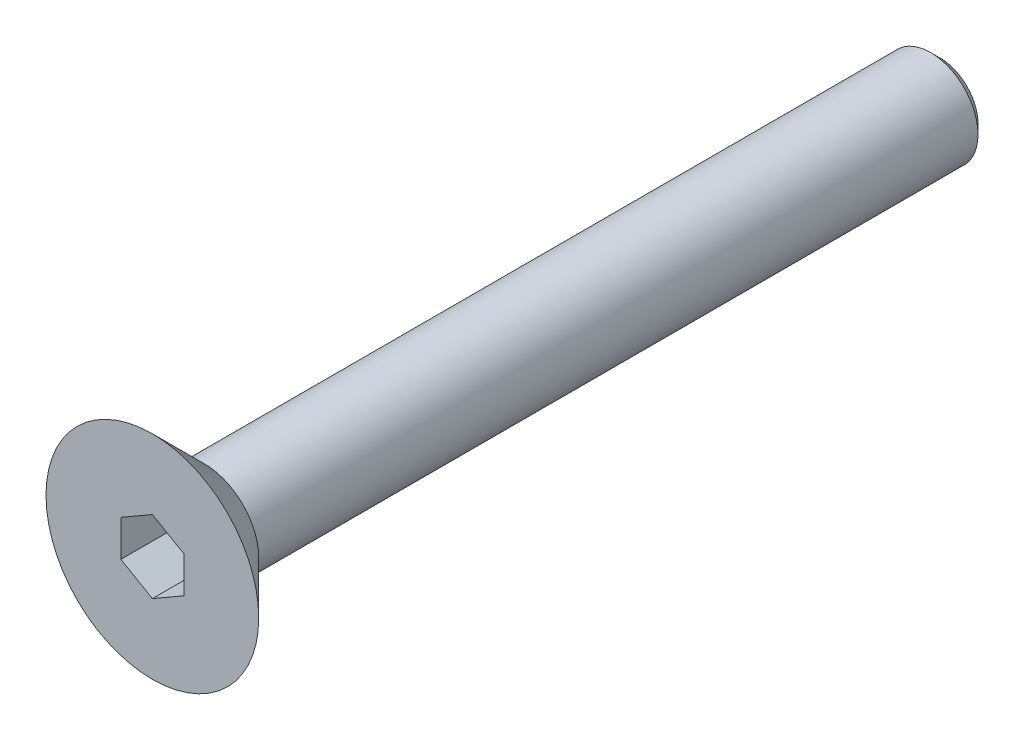
SolidWorks part; units mm, degrees
ref_plane "Front Plane" through (0, 0, 0) normal (0, 0, 1) x (1, 0, 0)
ref_plane "Top Plane" through (0, 0, 0) normal (0, 1, 0) x (1, 0, 0)
ref_plane "Right Plane" through (0, 0, 0) normal (1, 0, 0) x (0, 0, -1)
sketch "Sketch1" plane through (0, 0, 0) normal (0, 0, 1) x (1, 0, 0)
  circle A0 centre (0, 0) radius 3.375
  dimension "D1" = 6.75
extrude "Boss-Extrude1" add sketch "Sketch1" along normal blind 1.65
sketch "Sketch2" plane through (0, 0, 0) normal (0, 0, -1) x (-1, 0, 0)
  circle A0 centre (0, 0) radius 1.5
  dimension "D1" = 3
extrude "Boss-Extrude2" add sketch "Sketch2" along normal blind 23.35
chamfer "Chamfer1" distance 0.3 angle 45 1 edges at (-1.5, 0, -23.35)
sketch "Sketch3" plane through (0, 0, 1.65) normal (0, 0, 1) x (1, 0, 0)
  line L1 (0, 1.1547) -> (-1, 0.5774)
  line L2 (-1, 0.5774) -> (-1, -0.5774)
  line L3 (-1, -0.5774) -> (0, -1.1547)
  line L4 (0, -1.1547) -> (1, -0.5774)
  line L5 (1, -0.5774) -> (1, 0.5774)
  line L6 (1, 0.5774) -> (0, 1.1547)
  circle A0 centre (0, 0) radius 1 construction
  dimension "D1" = 2
extrude "Cut-Extrude1" cut sketch "Sketch3" against normal blind 2
chamfer "Chamfer2" distance 1.65 angle 45 1 edges at (3.375, 0, 0)
